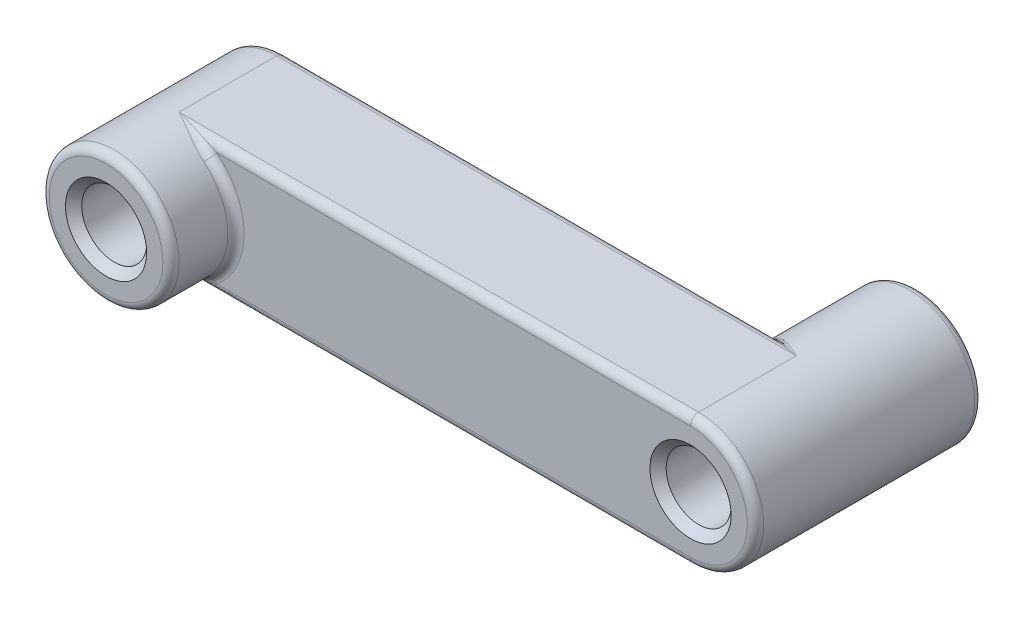
SolidWorks part; units mm, degrees
ref_plane "Plano frontal" through (0, 0, 0) normal (0, 0, 1) x (1, 0, 0)
ref_plane "Plano superior" through (0, 0, 0) normal (0, 1, 0) x (1, 0, 0)
ref_plane "Plano direito" through (0, 0, 0) normal (1, 0, 0) x (0, 0, -1)
sketch "Esboço1" plane through (0, 0, 0) normal (0, 0, 1) x (1, 0, 0)
  line L0 (-32, 0) -> (0, 0) construction
  line L1 (0, 0) -> (-32, 0) construction
  line L8 (0, -4) -> (-32, -4)
  line L9 (0, 4) -> (-32, 4)
  circle A0 centre (0, 0) radius 2
  circle A1 centre (-32, 0) radius 2
  arc A4 (0, -4) -> (0, 4) centre (0, 0) ccw
  arc A5 (-32, 4) -> (-32, -4) centre (-32, 0) ccw
  point P6 (-16, 0)
  dimension "D1" = 4
  dimension "D4" = 4
  dimension "D6" = 4
  dimension "D2" = 32
extrude "Ressalto-extrusão1" add sketch "Esboço1" along normal blind 18
sketch "Esboço2" plane through (0, 0, 0) normal (0, 0, -1) x (-1, 0, 0)
  circle A0 centre (0, 0) radius 4
extrude "Corte-extrusão1" cut sketch "Esboço2" against normal blind 7 flip side to cut
sketch "Esboço3" plane through (0, 0, 18) normal (0, 0, 1) x (1, 0, 0)
  circle A0 centre (-32, 0) radius 4
extrude "Corte-extrusão2" cut sketch "Esboço3" against normal blind 4 flip side to cut
fillet "Filete1" radius 0.5 8 edges at (-16, -4, 7) (-36, 0, 7) (-28, 0, 18) (4, 0, 0) (-16, 4, 7) (-16, 4, 14) (4, 0, 14) (-16, -4, 14)
chamfer "Chanfro1" distance 0.5 angle 45 4 edges at (-34, 0, 7) (-30, 0, 18) (2, 0, 14) (2, 0, 0)
fillet "Filete2" radius 0.5 6 edges at (-30.7802, -3.8095, 13.8927) (-30.7802, 3.8095, 13.8927) (-1.2198, -3.8095, 7.1073) (-1.2198, 3.8095, 7.1073) (-28, 0, 14) (-4, 0, 7)
